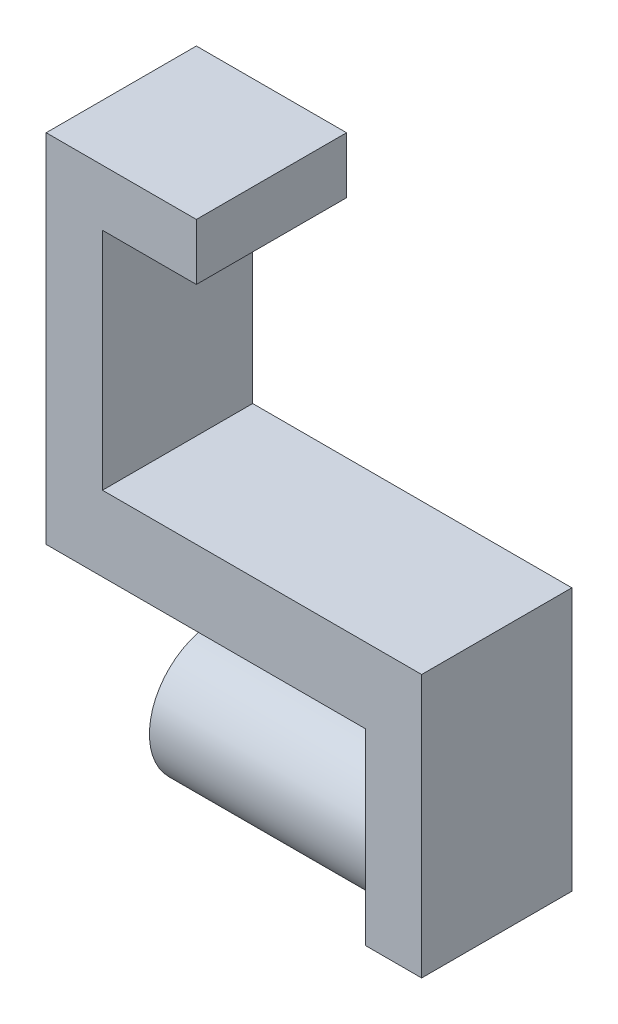
SolidWorks part; units mm, degrees
material "ASTM A36 Steel"
ref_plane "Front Plane" through (0, 0, 0) normal (0, 0, 1) x (1, 0, 0)
ref_plane "Top Plane" through (0, 0, 0) normal (0, 1, 0) x (1, 0, 0)
ref_plane "Right Plane" through (0, 0, 0) normal (1, 0, 0) x (0, 0, -1)
sketch "Sketch1" plane through (0, 0, 0) normal (1, 0, 0) x (0, 0, -1)
  circle A0 centre (0, 0) radius 11.1125
extrude "Boss-Extrude1" add sketch "Sketch1" against normal blind 38.1
sketch "Sketch2" plane through (0, 0, 0) normal (0, 0, 1) x (1, 0, 0)
  line L1 (0, -11.1125) -> (9.525, -11.1125)
  line L2 (0, -11.1125) -> (0, 20.6375)
  line L3 (0, 20.6375) -> (9.525, 20.6375)
  line L4 (9.525, -11.1125) -> (9.525, 20.6375)
extrude "Boss-Extrude2" add sketch "Sketch2" along normal blind 12.7 and the other way blind 12.7
sketch "Sketch3" plane through (0, 0, 0) normal (0, 0, 1) x (1, 0, 0)
  line L1 (-53.975, 20.6375) -> (9.525, 20.6375)
  line L2 (-53.975, 20.6375) -> (-53.975, 33.3375)
  line L3 (-53.975, 33.3375) -> (9.525, 33.3375)
  line L4 (9.525, 20.6375) -> (9.525, 33.3375)
extrude "Boss-Extrude3" add sketch "Sketch3" along normal blind 12.7 and the other way blind 12.7
sketch "Sketch4" plane through (0, 0, 0) normal (0, 0, 1) x (1, 0, 0)
  line L1 (-53.975, 20.6375) -> (-44.45, 20.6375)
  line L2 (-53.975, 20.6375) -> (-53.975, 80.9371)
  line L3 (-53.975, 80.9371) -> (-44.45, 80.9371)
  line L4 (-44.45, 20.6375) -> (-44.45, 80.9371)
extrude "Boss-Extrude4" add sketch "Sketch4" along normal blind 12.7 and the other way blind 12.7
sketch "Sketch5" plane through (0, 0, 0) normal (0, 0, 1) x (1, 0, 0)
  line L0 (-53.975, 80.9371) -> (-53.975, 20.6375) construction
  line L1 (-53.975, 71.4121) -> (-28.575, 71.4121)
  line L2 (-53.975, 71.4121) -> (-53.975, 80.9371)
  line L3 (-53.975, 80.9371) -> (-28.575, 80.9371)
  line L4 (-28.575, 71.4121) -> (-28.575, 80.9371)
extrude "Boss-Extrude5" add sketch "Sketch5" along normal blind 12.7 and the other way blind 12.7
